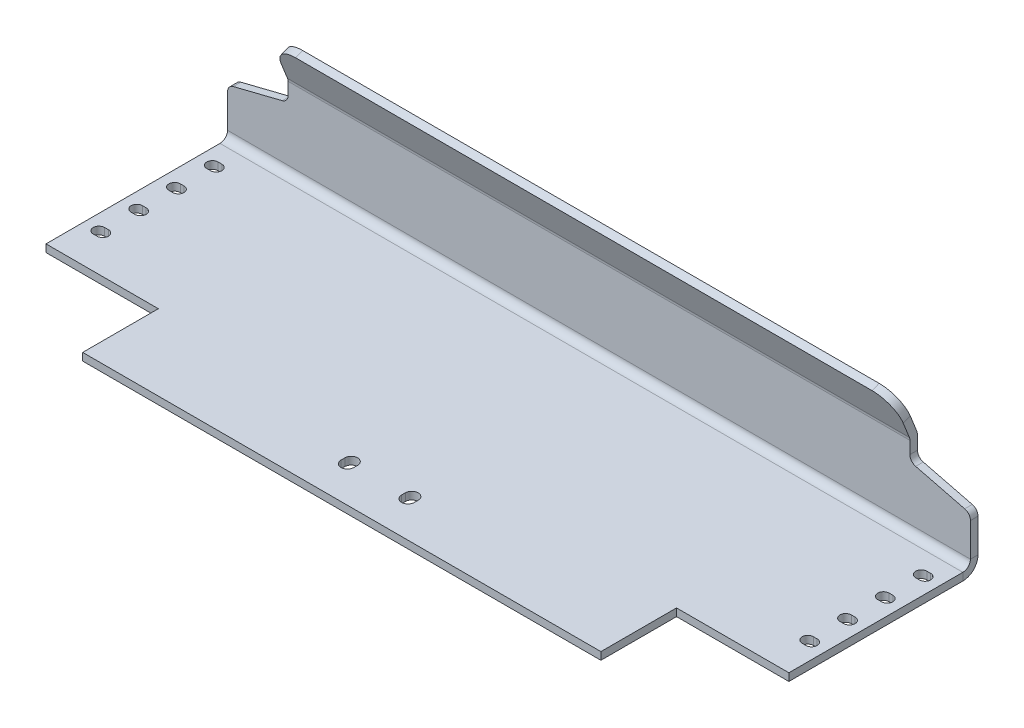
SolidWorks part; units mm, degrees
note: The reader was unsure of these and kept them because the rebuilt part matched: thickness of "基体-法兰1", "钣金6", "钣金10", "钣金11", "钣金12", "钣金13", "钣金14"; bend radius of "基体折弯1", "基体折弯2".
material "Q355"
ref_plane "前视基准面" through (0, 0, 0) normal (0, 0, 1) x (1, 0, 0)
ref_plane "上视基准面" through (0, 0, 0) normal (0, 1, 0) x (1, 0, 0)
ref_plane "右视基准面" through (0, 0, 0) normal (1, 0, 0) x (0, 0, -1)
sketch "草图1" plane through (0, 0, 0) normal (1, 0, 0) x (0, 0, -1)
  line L0 (0, 0) -> (240, 0)
  line L1 (240, 0) -> (240, 108)
  line L2 (240, 108) -> (220, 158)
  dimension "D1" = 240
  dimension "D2" = 108
  dimension "D3" = 50
  dimension "D4" = 20
base flange "基体-法兰1" sketch "草图1" end condition mid plane depth 982 reverse direction no thickness 10 reverse thickness direction no bend radius 10
bend "基体折弯1" bend radius 10 bend angle 21.801 parameters "D5"=1
bend "基体折弯2" bend radius 10 bend angle 90 parameters "D5"=2
sketch "草图2" plane through (0, 0, -250) normal (0, 0, -1) x (-1, 0, 0)
  line L0 (-411, 161.7139) -> (-411, 82)
  line L1 (-491, 161.7139) -> (491, 161.7139) construction
  line L2 (-411, 82) -> (-491, 62)
  line L4 (-491, 62) -> (-491, 161.7139)
  line L5 (491, 161.7139) -> (411, 161.7139)
  line L6 (411, 161.7139) -> (411, 82)
  line L7 (411, 82) -> (491, 62)
  line L8 (491, 10) -> (491, 106.0742) construction
  line L9 (491, 62) -> (491, 161.7139)
  line L10 (-491, 161.7139) -> (-411, 161.7139)
  line L12 (-491, 10) -> (-491, 106.0742) construction
  line L13 (-491, -10) -> (491, -10) construction
  dimension "D1" = 72
  dimension "D2" = 80
  dimension "D3" = 92
extrude "切除-拉伸1" cut sketch "草图2" against normal up to next
sketch "草图3" plane through (0, 0, 0) normal (0, 1, 0) x (1, 0, 0)
  line L0 (466, 50) -> (471, 50) construction
  line L1 (466, 57.5) -> (471, 57.5)
  line L2 (466, 42.5) -> (471, 42.5)
  line L3 (491, 0) -> (-491, 0) construction
  line L5 (-466, 50) -> (-471, 50) construction
  line L6 (-466, 42.5) -> (-471, 42.5)
  line L7 (-466, 57.5) -> (-471, 57.5)
  line L8 (0, 0) -> (0, 250) construction
  line L9 (411, 250) -> (-411, 250) construction
  arc A0 (466, 57.5) -> (466, 42.5) centre (466, 50) ccw
  arc A1 (471, 42.5) -> (471, 57.5) centre (471, 50) ccw
  arc A2 (-466, 42.5) -> (-466, 57.5) centre (-466, 50) ccw
  arc A3 (-471, 57.5) -> (-471, 42.5) centre (-471, 50) ccw
  point P2 (468.5, 50)
  point P12 (-468.5, 50)
  dimension "D2" = 5
  dimension "D1" = 7.5
  dimension "D3" = 50
  dimension "D4" = 937
extrude "切除-拉伸2" cut sketch "草图3" against normal through all
pattern_linear "阵列(线性)1" count 4 spacing 50 along (0, 0, -1) of "切除-拉伸2"
fillet "圆角1" radius 30 2 edges at (-411, 159.857, -224.6424) (411, 159.857, -224.6424)
sketch "草图4" plane through (0, 0, 0) normal (0, 1, 0) x (1, 0, 0)
  line L0 (491, 0) -> (-491, 0) construction
  line L1 (-342.5, 0) -> (342.5, 0)
  line L3 (-342.5, -100) -> (342.5, -100)
  line L5 (0, 0) -> (0, -100) construction
  line L6 (-342.5, 0) -> (-342.5, -100)
  line L7 (342.5, 0) -> (342.5, -100)
  dimension "D1" = 685
  dimension "D2" = 685
  dimension "D3" = 100
extrude "凸台-拉伸1" add sketch "草图4" against normal blind 10
sketch "草图5" plane through (0, 0, 0) normal (0, 1, 0) x (1, 0, 0)
  line L0 (-342.5, -100) -> (342.5, -100) construction
  line L1 (0, 0) -> (0, -50) construction
  line L3 (-40, -47.5) -> (-40, -52.5) construction
  line L4 (-31.5, -47.5) -> (-31.5, -52.5)
  line L5 (-48.5, -47.5) -> (-48.5, -52.5)
  line L6 (40, -47.5) -> (40, -52.5) construction
  line L10 (48.5, -47.5) -> (48.5, -52.5)
  line L11 (31.5, -47.5) -> (31.5, -52.5)
  line L12 (-40, -50) -> (40, -50) construction
  arc A2 (-31.5, -47.5) -> (-48.5, -47.5) centre (-40, -47.5) ccw
  arc A3 (-48.5, -52.5) -> (-31.5, -52.5) centre (-40, -52.5) ccw
  arc A6 (48.5, -47.5) -> (31.5, -47.5) centre (40, -47.5) ccw
  arc A7 (31.5, -52.5) -> (48.5, -52.5) centre (40, -52.5) ccw
  point P1 (40, -50)
  point P11 (-40, -50)
  dimension "D1" = 50
  dimension "D2" = 80
  dimension "D3" = 8.5
  dimension "D4" = 5
  dimension "D5" = 5
extrude "切除-拉伸3" cut sketch "草图5" against normal blind 10 normal cut yes
fillet "圆角2" radius 10 4 edges at (-491, 62, -245) (-411, 82, -245) (411, 82, -245) (491, 62, -245)
sketch "折弯-线1" [suppressed] plane through (0, 0, 0) normal (0, 1, 0) x (1, 0, 0)
sketch "边界框1" [suppressed] plane through (0, 0, 0) normal (0, 1, 0) x (1, 0, 0)
sheet metal parameters "钣金6" thickness 10 parameters "D1"=12, "D7"=12
flat pattern "平板型式6" [suppressed]
sketch "折弯-线2" plane through (0, 0, 0) normal (0, 1, 0) x (1, 0, 0)
  line L0 (0, 202.1372) -> (825, 202.1372) construction
  line L1 (0, 305.3879) -> (825, 305.3879) construction
  line L2 (0, 202.1372) -> (825, 202.1372) construction
  line L3 (0, 305.3879) -> (825, 305.3879) construction
sketch3d "边界框2" [suppressed]
  line L0 (0, 0, 0) -> (-825, 0, 0) construction
  line L1 (0, 360.3531, 0) -> (-825, 360.3531, 0) construction
  line L2 (0, 0, 0) -> (0, 360.3531, 0) construction
  line L3 (-825, 0, 0) -> (-825, 360.3531, 0) construction
bend of the flat pattern "展开-<基体折弯1>1"
bend of the flat pattern "展开-<基体折弯2>1"
sheet metal parameters "钣金10" thickness 10 parameters "D1"=12, "D7"=12
flat pattern "平板型式6"
sketch "折弯-线2" plane through (0, 0, 0) normal (0, 1, 0) x (1, 0, 0)
  line L0 (0, 202.1372) -> (825, 202.1372) construction
  line L1 (0, 305.3879) -> (825, 305.3879) construction
  line L2 (0, 202.1372) -> (825, 202.1372) construction
  line L3 (0, 305.3879) -> (825, 305.3879) construction
sketch3d "边界框2" [suppressed]
  line L0 (0, 0, 0) -> (-825, 0, 0) construction
  line L1 (0, 360.3531, 0) -> (-825, 360.3531, 0) construction
  line L2 (0, 0, 0) -> (0, 360.3531, 0) construction
  line L3 (-825, 0, 0) -> (-825, 360.3531, 0) construction
bend of the flat pattern "展开-<基体折弯1>1"
bend of the flat pattern "展开-<基体折弯2>1"
sheet metal parameters "钣金11" thickness 10 parameters "D1"=12, "D7"=12
flat pattern "平板型式6"
sketch "折弯-线2" plane through (0, 0, 0) normal (0, 1, 0) x (1, 0, 0)
  line L0 (0, 202.1372) -> (825, 202.1372) construction
  line L1 (0, 305.3879) -> (825, 305.3879) construction
  line L2 (0, 202.1372) -> (825, 202.1372) construction
  line L3 (0, 305.3879) -> (825, 305.3879) construction
sketch3d "边界框2" [suppressed]
  line L0 (0, 0, 0) -> (-825, 0, 0) construction
  line L1 (0, 360.3531, 0) -> (-825, 360.3531, 0) construction
  line L2 (0, 0, 0) -> (0, 360.3531, 0) construction
  line L3 (-825, 0, 0) -> (-825, 360.3531, 0) construction
bend of the flat pattern "展开-<基体折弯1>1"
bend of the flat pattern "展开-<基体折弯2>1"
sheet metal parameters "钣金12" thickness 10 parameters "D1"=12, "D7"=12
flat pattern "平板型式6"
sketch "折弯-线2" plane through (0, 0, 0) normal (0, 1, 0) x (1, 0, 0)
  line L0 (0, 202.1372) -> (825, 202.1372) construction
  line L1 (0, 305.3879) -> (825, 305.3879) construction
  line L2 (0, 202.1372) -> (825, 202.1372) construction
  line L3 (0, 305.3879) -> (825, 305.3879) construction
sketch3d "边界框2" [suppressed]
  line L0 (0, 0, 0) -> (-825, 0, 0) construction
  line L1 (0, 360.3531, 0) -> (-825, 360.3531, 0) construction
  line L2 (0, 0, 0) -> (0, 360.3531, 0) construction
  line L3 (-825, 0, 0) -> (-825, 360.3531, 0) construction
bend of the flat pattern "展开-<基体折弯1>1"
bend of the flat pattern "展开-<基体折弯2>1"
sheet metal parameters "钣金13" thickness 10 parameters "D1"=12, "D7"=12
flat pattern "平板型式6"
sketch "折弯-线2" plane through (0, 0, 0) normal (0, 1, 0) x (1, 0, 0)
  line L0 (0, 202.1372) -> (825, 202.1372) construction
  line L1 (0, 305.3879) -> (825, 305.3879) construction
  line L2 (0, 202.1372) -> (825, 202.1372) construction
  line L3 (0, 305.3879) -> (825, 305.3879) construction
sketch3d "边界框2" [suppressed]
  line L0 (0, 0, 0) -> (-825, 0, 0) construction
  line L1 (0, 360.3531, 0) -> (-825, 360.3531, 0) construction
  line L2 (0, 0, 0) -> (0, 360.3531, 0) construction
  line L3 (-825, 0, 0) -> (-825, 360.3531, 0) construction
bend of the flat pattern "展开-<基体折弯1>1"
bend of the flat pattern "展开-<基体折弯2>1"
sheet metal parameters "钣金14" thickness 10 parameters "D1"=12, "D7"=12
flat pattern "平板型式6"
sketch "折弯-线2" plane through (0, 0, 0) normal (0, 1, 0) x (1, 0, 0)
  line L0 (-491, 241.781) -> (491, 241.781) construction
  line L1 (-411, 352.4899) -> (411, 352.4899) construction
  line L2 (-491, 241.781) -> (491, 241.781) construction
  line L3 (-411, 352.4899) -> (411, 352.4899) construction
sketch3d "边界框2" [suppressed]
  line L0 (-982, -100, 0) -> (0, -100, 0) construction
  line L1 (-982, 407.2695, 0) -> (0, 407.2695, 0) construction
  line L2 (-982, -100, 0) -> (-982, 407.2695, 0) construction
  line L3 (0, -100, 0) -> (0, 407.2695, 0) construction
bend of the flat pattern "展开-<基体折弯1>1"
bend of the flat pattern "展开-<基体折弯2>1"
